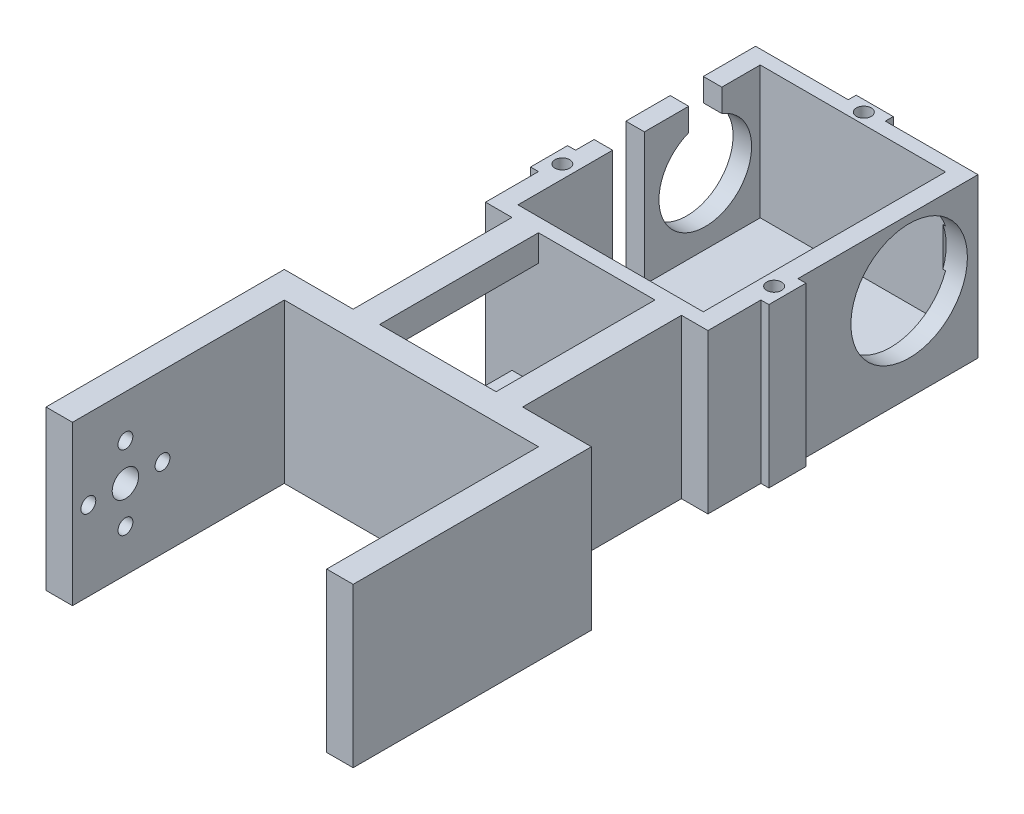
SolidWorks part; units mm, degrees
ref_plane "Front Plane" through (0, 0, 0) normal (0, 0, 1) x (1, 0, 0)
ref_plane "Top Plane" through (0, 0, 0) normal (0, 1, 0) x (1, 0, 0)
ref_plane "Right Plane" through (0, 0, 0) normal (1, 0, 0) x (0, 0, -1)
sketch "Sketch1" plane through (0, 0, 0) normal (0, 1, 0) x (1, 0, 0)
  line L1 (-21, 25.5) -> (21, 25.5)
  line L2 (-21, 25.5) -> (-21, -25.5)
  line L3 (-21, -25.5) -> (21, -25.5)
  line L4 (21, 25.5) -> (21, -25.5)
  line L5 (-11, -25.5) -> (-16, -25.5)
  line L6 (-11, -25.5) -> (-11, -55.5)
  line L7 (-11, -55.5) -> (-16, -55.5)
  line L8 (-16, -25.5) -> (-16, -55.5)
  line L9 (16, -25.5) -> (11, -25.5)
  line L10 (16, -25.5) -> (16, -55.5)
  line L11 (16, -55.5) -> (11, -55.5)
  line L12 (11, -25.5) -> (11, -55.5)
  line L13 (-29, -55.5) -> (29, -55.5)
  line L14 (-29, -55.5) -> (-29, -60.5)
  line L15 (-29, -60.5) -> (29, -60.5)
  line L16 (29, -55.5) -> (29, -60.5)
  line L17 (-24, -60.5) -> (-29, -60.5)
  line L18 (-24, -60.5) -> (-24, -100.5)
  line L19 (-24, -100.5) -> (-29, -100.5)
  line L20 (-29, -60.5) -> (-29, -100.5)
  line L21 (29, -60.5) -> (24, -60.5)
  line L22 (29, -60.5) -> (29, -100.5)
  line L23 (29, -100.5) -> (24, -100.5)
  line L24 (24, -60.5) -> (24, -100.5)
  point P4 (-21, 0)
  point P6 (0, 25.5)
  point P12 (0, -25.5)
  point P21 (0, -55.5)
  dimension "D1" = 42
  dimension "D2" = 51
  dimension "D3" = 5
  dimension "D4" = 30
  dimension "D5" = 5
  dimension "D6" = 5
  dimension "D7" = 5
  dimension "D8" = 58
  dimension "D9" = 40
extrude "Boss-Extrude1" add sketch "Sketch1" along normal blind 5 contours L4 L1 L2 L3 region at (0, 0, 0)
sketch "Sketch3" plane through (0, 5, 0) normal (0, 1, 0) x (1, 0, 0)
  line L1 (-17.5, 22.875) -> (17.5, 22.875)
  line L2 (-17.5, 22.875) -> (-17.5, -22.875)
  line L3 (-17.5, -22.875) -> (17.5, -22.875)
  line L4 (17.5, 22.875) -> (17.5, -22.875)
  line L5 (-21, 25.5) -> (21, 25.5)
  line L6 (-21, 25.5) -> (-21, -25.5)
  line L7 (-21, -25.5) -> (21, -25.5)
  line L8 (21, 25.5) -> (21, -25.5)
  point P4 (-17.5, 0)
  point P6 (0, 22.875)
  dimension "D1" = 35
  dimension "D2" = 45.75
extrude "Boss-Extrude3" add sketch "Sketch3" along normal blind 25
sketch "Sketch4" plane through (-21, 0, 0) normal (-1, 0, 0) x (0, 0, 1)
  line L1 (-25.5, 30) -> (25.5, 30) construction
  line L2 (0, 30) -> (0, 0) construction
  circle A0 centre (-12.5, 17.5) radius 8.75
  dimension "D2" = 17.5
  dimension "D1" = 12.5
  dimension "D3" = 12.5
extrude "Cut-Extrude2" cut sketch "Sketch4" against normal blind 5
sketch "Sketch6" plane through (-17.5, 0, 0) normal (1, 0, 0) x (0, 0, -1)
  line L0 (-25.5, 30) -> (25.5, 30) construction
  line L2 (0, 30) -> (0, 0) construction
  line L4 (9.375, 17.5) -> (9.375, 30)
  line L5 (9.375, 30) -> (15.625, 30)
  line L6 (15.625, 17.5) -> (15.625, 30)
  line L7 (25.5, 0) -> (-25.5, 0) construction
  arc A0 (9.375, 17.5) -> (15.625, 17.5) centre (12.5, 17.5) ccw
  point P11 (12.5, 30)
  dimension "D1" = 6.25
  dimension "D2" = 12.5
  dimension "D3" = 12.5
extrude "Cut-Extrude3" cut sketch "Sketch6" against normal blind 4
sketch "Sketch7" plane through (-21, 0, 0) normal (-1, 0, 0) x (0, 0, 1)
  line L0 (-9.375, 30) -> (25.5, 30) construction
  line L1 (-1, 30) -> (5, 30)
  line L2 (-1, 30) -> (-1, 5)
  line L3 (-1, 5) -> (5, 5)
  line L4 (5, 30) -> (5, 5)
  line L6 (25.5, 30) -> (25.5, 0) construction
  line L7 (-25.5, 0) -> (25.5, 0) construction
  dimension "D1" = 20.5
  dimension "D2" = 5
  dimension "D3" = 6
extrude "Cut-Extrude4" cut sketch "Sketch7" against normal blind 4
sketch "Sketch9" plane through (21, 0, 0) normal (1, 0, 0) x (0, 0, -1)
  line L0 (25.5, 30) -> (25.5, 0) construction
  line L1 (-25.5, 30) -> (25.5, 30) construction
  circle A0 centre (12.5, 17.5) radius 11
  dimension "D2" = 22
  dimension "D1" = 13
  dimension "D3" = 12.5
extrude "Cut-Extrude5" cut sketch "Sketch9" against normal blind 4
sketch "Sketch16" plane through (-21, 0, 0) normal (-1, 0, 0) x (0, 0, 1)
  line L0 (5, 30) -> (25.5, 30) construction
  line L1 (15.5, 30) -> (8.5, 30)
  line L2 (15.5, 30) -> (15.5, 0)
  line L3 (15.5, 0) -> (8.5, 0)
  line L4 (8.5, 30) -> (8.5, 0)
  line L5 (-25.5, 0) -> (25.5, 0) construction
  line L6 (25.5, 30) -> (25.5, 0) construction
  dimension "D1" = 10
  dimension "D2" = 7
extrude "Boss-Extrude5" add sketch "Sketch16" along normal blind 1.5
sketch "Sketch17" plane through (21, 0, 0) normal (1, 0, 0) x (0, 0, -1)
  line L0 (-25.5, 30) -> (25.5, 30) construction
  line L1 (-15.5, 30) -> (-8.5, 30)
  line L2 (-15.5, 30) -> (-15.5, 0)
  line L3 (-15.5, 0) -> (-8.5, 0)
  line L4 (-8.5, 30) -> (-8.5, 0)
  line L5 (25.5, 0) -> (-25.5, 0) construction
  line L6 (-25.5, 30) -> (-25.5, 0) construction
  dimension "D1" = 10
  dimension "D2" = 7
extrude "Boss-Extrude6" add sketch "Sketch17" along normal blind 1.5
sketch "Sketch19" plane through (0, 0, -25.5) normal (0, 0, -1) x (-1, 0, 0)
  line L0 (-21, 30) -> (21, 30) construction
  line L1 (3.5, 30) -> (-3.5, 30)
  line L2 (3.5, 30) -> (3.5, 0)
  line L3 (3.5, 0) -> (-3.5, 0)
  line L4 (-3.5, 30) -> (-3.5, 0)
  line L5 (21, 0) -> (-21, 0) construction
  point P8 (0, 0)
  point P9 (0, 30)
  dimension "D1" = 7
extrude "Boss-Extrude7" add sketch "Sketch19" along normal blind 1.5
sketch "Sketch18" plane through (0, 30, 0) normal (0, 1, 0) x (1, 0, 0)
  line L0 (-22.5, -15.5) -> (-22.5, -8.5) construction
  line L1 (0, -19.5533) -> (0, 11.7982) construction
  line L2 (-3.5, 27) -> (3.5, 27) construction
  line L3 (-22.5, -12) -> (-17.5, -12) construction
  line L4 (-17.5, -5) -> (-17.5, -22.875) construction
  line L5 (0, 27) -> (0, 22.875) construction
  line L6 (17.5, 22.875) -> (-17.5, 22.875) construction
  circle A0 centre (-20, -12) radius 1.4
  circle A1 centre (20, -12) radius 1.4
  circle A2 centre (0, 24.9375) radius 1.4
  point P5 (-22.5, -12)
  point P17 (0, 27)
  point P21 (-20, -12)
  point P26 (0, 24.9375)
  dimension "D1" = 2.8
extrude "Cut-Extrude7" cut sketch "Sketch18" against normal blind 6
extrude "Boss-Extrude8" add sketch "Sketch1<3>" along normal blind 30 contours L3 L8 L7 L6 | L3 L12 L11 L10 | L16 L13 L11 L7 L14 L15 | L15 L24 L23 L22 | L15 L20 L19 L18
sketch "Sketch1<3>" plane through (0, 0, 0) normal (0, 1, 0) x (1, 0, 0) same geometry as "Sketch1"
sketch "Sketch21" plane through (24, 0, 0) normal (-1, 0, 0) x (0, 0, 1)
  line L0 (100.5, 30) -> (100.5, 0) construction
  circle A0 centre (90.5, 15) radius 2.95
  point P6 (100.5, 15)
  dimension "D1" = 5.9
  dimension "D2" = 10
extrude "Boss-Extrude9" add sketch "Sketch21" along normal blind 4
sketch "Sketch24" plane through (-16, 0, 0) normal (-1, 0, 0) x (0, 0, 1)
  line L0 (25.5, 30) -> (25.5, 0) construction
  line L1 (25.5, 25) -> (55.5, 25)
  line L2 (25.5, 25) -> (25.5, 5)
  line L3 (25.5, 5) -> (55.5, 5)
  line L4 (55.5, 25) -> (55.5, 5)
  line L5 (55.5, 30) -> (55.5, 0) construction
  point P8 (25.5, 15)
  point P9 (25.5, 15)
  dimension "D1" = 20
extrude "Cut-Extrude8" cut sketch "Sketch24" against normal blind 30
sketch "Sketch25" plane through (-29, 0, 0) normal (-1, 0, 0) x (0, 0, 1)
  line L0 (90.5, 22) -> (90.5, 15) construction
  line L1 (90.5, 15) -> (83.5, 15) construction
  circle A0 centre (90.5, 15) radius 2.5
  circle A1 centre (90.5, 15) radius 2.95 construction
  circle A2 centre (90.5, 22) radius 1.4
  circle A3 centre (83.5, 15) radius 1.4
  circle A4 centre (90.5, 8) radius 1.4
  circle A5 centre (97.5, 15) radius 1.4
  dimension "D1" = 5
  dimension "D3" = 2.8
  dimension "D2" = 7
extrude "Cut-Extrude9" cut sketch "Sketch25" against normal blind 5
